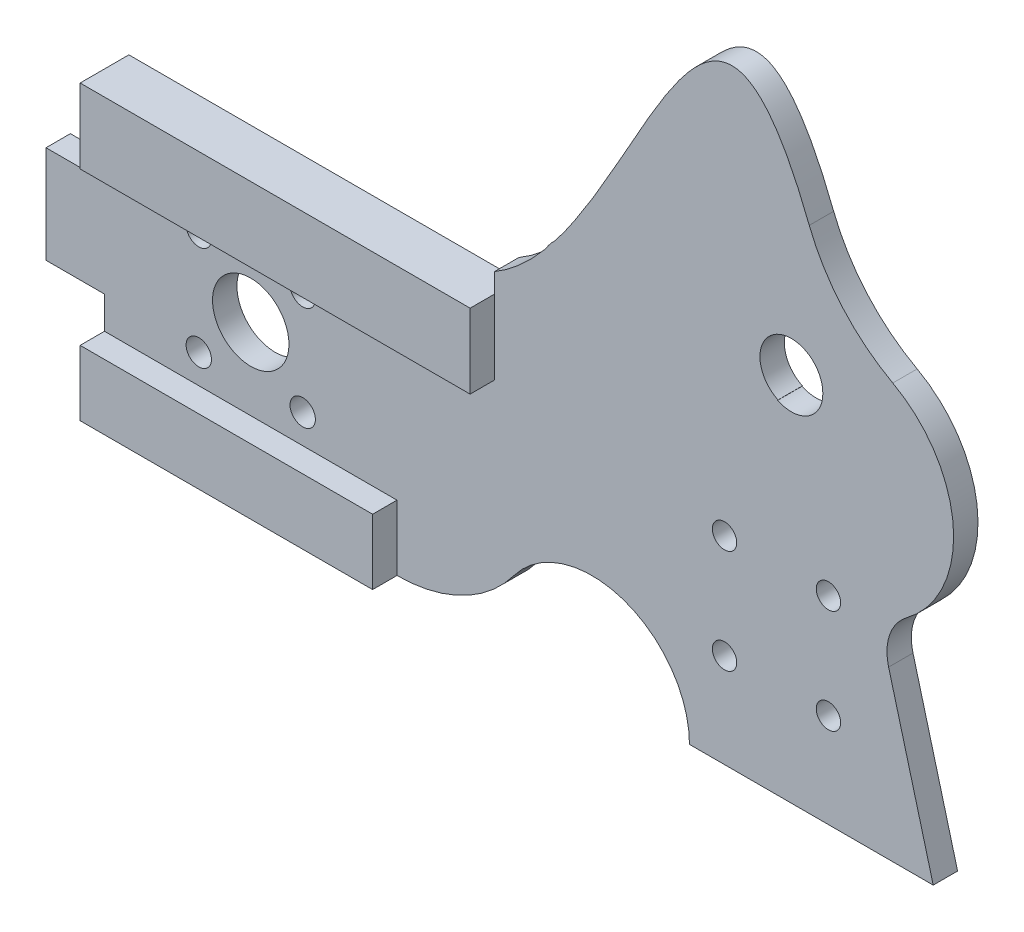
SolidWorks part; units mm, degrees
ref_plane "Front Plane" through (0, 0, 0) normal (0, 0, 1) x (1, 0, 0)
ref_plane "Top Plane" through (0, 0, 0) normal (0, 1, 0) x (1, 0, 0)
ref_plane "Right Plane" through (0, 0, 0) normal (1, 0, 0) x (0, 0, -1)
sketch "Sketch1" plane through (0, 0, 0) normal (0, 0, 1) x (1, 0, 0)
  line L0 (0, 0) -> (107.95, 0)
  line L3 (0, 38.1) -> (0, 25.4)
  line L4 (95.3675, 55.88) -> (0, 38.1)
  line L5 (0, 19.05) -> (100.2273, 19.05) construction
  line L6 (19.05, 19.05) -> (19.05, 28.62) construction
  line L7 (19.05, 19.05) -> (25.817, 25.817) construction
  line L8 (107.95, 0) -> (100.9363, 26.1756)
  line L10 (0, 12.7) -> (0, 0)
  line L11 (0, 25.4) -> (-7.62, 25.4)
  line L13 (0, 12.7) -> (-7.62, 12.7)
  line L14 (-7.62, 25.4) -> (-7.62, 12.7)
  line L15 (100.9363, 26.1756) -> (100.8688, 26.4276)
  arc A0 (100.8688, 26.4276) -> (95.3675, 55.88) centre (95.3675, 40.64) ccw
  circle A1 centre (95.3675, 40.64) radius 4.0957 construction
  circle A2 centre (19.05, 19.05) radius 9.57 construction
  circle A3 centre (25.817, 25.817) radius 1.651
  circle A4 centre (25.817, 12.283) radius 1.651
  circle A5 centre (12.283, 12.283) radius 1.651
  circle A6 centre (12.283, 25.817) radius 1.651
  circle A7 centre (89.4701, 48.2476) radius 4.0958
  point P26 (19.05, 19.05)
  dimension "D1" = 8.1915
  dimension "D5" = 15.24
  dimension "D4" = 19.14
  dimension "D7" = 3.302
  dimension "D11" = 97.0107
  dimension "D2" = 38.1
  dimension "D6" = 107.95
  dimension "D8" = 45
  dimension "D9" = 4
  dimension "D10" = 19.05
  dimension "D12" = 75
  dimension "D14" = 12.7
  dimension "D15" = 12.7
  dimension "D16" = 7.62
extrude "Boss-Extrude1" add sketch "Sketch1" along normal blind 3.175
sketch "Sketch2" plane through (0, 0, 3.175) normal (0, 0, 1) x (1, 0, 0)
  circle A0 centre (95.3675, 40.64) radius 38.1 construction
sketch "Sketch6" plane through (0, 0, 3.175) normal (0, 0, 1) x (1, 0, 0)
  line L0 (0, 0) -> (107.95, 0) construction
  line L1 (50.8, 0) -> (76.2, 0)
  arc A0 (76.2, 0) -> (50.8, 0) centre (63.5, 0) ccw
  dimension "D1" = 25.4
  dimension "D2" = 31.75
extrude "Cut-Extrude2" cut sketch "Sketch6" against normal blind 6.35
sketch "Sketch7" plane through (0, 0, 3.175) normal (0, 0, 1) x (1, 0, 0)
  line L0 (12.283, 25.817) -> (25.817, 12.283) construction
  line L1 (12.283, 12.283) -> (25.817, 25.817) construction
  line L2 (12.283, 25.817) -> (78.4839, 25.817) construction
  line L3 (11.7326, 12.283) -> (12.283, 12.283) construction
  circle A0 centre (19.05, 19.05) radius 4.9784
  circle A4 centre (80.7666, 12.283) radius 1.5875
  circle A5 centre (94.2997, 12.283) radius 1.5875
  circle A6 centre (80.7666, 25.817) radius 1.5875
  circle A7 centre (94.2997, 25.817) radius 1.5875
  dimension "D1" = 9.9568
  dimension "D2" = 3.175
  dimension "D3" = 13.5331
extrude "Cut-Extrude3" cut sketch "Sketch7" against normal through all
fillet "Fillet1" radius 6.35 1 edges at (100.8688, 26.4276, 1.5875)
sketch "Sketch8" plane through (0, 0, 3.175) normal (0, 0, 1) x (1, 0, 0)
  line L1 (0, 38.1) -> (50.8, 38.1)
  line L2 (0, 38.1) -> (0, 50.8)
  line L3 (0, 50.8) -> (50.8, 50.8)
  line L4 (50.8, 38.1) -> (50.8, 50.8)
  dimension "D1" = 50.8
  dimension "D2" = 12.7
extrude "Cut-Extrude4" cut sketch "Sketch8" against normal blind 50.8
sketch "Sketch9" plane through (0, 0, 3.175) normal (0, 0, 1) x (1, 0, 0)
  line L3 (50.8, 40.64) -> (57.15, 40.64)
  line L5 (57.15, 40.64) -> (50.8, 40.64)
  line L6 (57.15, 40.64) -> (57.15, 50.8)
  line L7 (57.15, 50.8) -> (50.8, 50.8)
  line L8 (50.8, 40.64) -> (50.8, 50.8)
  line L9 (0, 38.1) -> (50.8, 38.1) construction
  line M8 (50.8, 47.571) -> (50.8, 38.1)
  line M21 (95.3675, 55.88) -> (50.8, 47.571)
  dimension "D1" = 10.16
  dimension "D2" = 2.54
  dimension "D3" = 6.35
extrude "Cut-Extrude5" cut sketch "Sketch9" against normal blind 19.304 contours L3 L6 M21 M8 region at (54.0583, 44.4092, 3.175)
fillet "Fillet6" radius 6.35 1 edges at (57.15, 40.64, 1.5875)
fillet "Fillet7" radius 6.35 1 edges at (57.15, 48.7549, 1.5875)
fillet "Fillet8" radius 19.05 1 edges at (50.8, 0, 1.5875)
sketch "Sketch12" plane through (0, 0, 3.175) normal (0, 0, 1) x (1, 0, 0)
  line L0 (107.95, 0) -> (146.812, 0) construction
  line L1 (8.0257, 45.4128) -> (80.6683, 75.7903) construction
  line L2 (95.3675, 40.64) -> (80.6683, 75.7903) construction
  line L3 (80.6683, 75.7903) -> (79.4434, 78.7195) construction
  line L4 (50.8, 40.64) -> (85.0271, 40.64)
  line L5 (85.0271, 40.64) -> (95.3675, 55.88)
  arc A0 (61.8128, 49.6242) -> (56.8883, 45.1859) centre (62.9766, 43.3817) ccw construction
  circle A1 centre (19.05, 19.05) radius 28.575 construction
  circle A2 centre (95.3675, 40.64) radius 38.1 construction
  circle A3 centre (80.6683, 75.7903) radius 3.175 construction
  spline S0 degree 3 poles (50.8, 40.64) (70.7778, 52.1788) (78.5943, 111.5434) (95.3675, 55.88) knots 0 0 0 0 1 1 1 1
  dimension "D2" = 6.35
  dimension "D1" = 38.862
extrude "Boss-Extrude2" add sketch "Sketch12" against normal blind 3.175
fillet "Fillet9" radius 24.13 1 edges at (95.3675, 55.88, 1.5875)
sketch "Sketch13" plane through (0, 0, 0) normal (0, 0, -1) x (-1, 0, 0)
  line L0 (0, 38.1) -> (0, 25.4) construction
  line L1 (-50.8, 38.1) -> (0, 38.1)
  line L2 (-50.8, 38.1) -> (-50.8, 28.4023)
  line L3 (-50.8, 28.4023) -> (0, 28.4023)
  line L4 (0, 38.1) -> (0, 28.4023)
  line L5 (0, 12.7) -> (0, 0) construction
  line L6 (0, 8.5046) -> (-38.1, 8.5046)
  line L7 (0, 8.5046) -> (0, 0)
  line L8 (0, 0) -> (-38.1, 0)
  line L9 (-38.1, 8.5046) -> (-38.1, 0)
extrude "Boss-Extrude3" add sketch "Sketch13" against normal blind 6.35
sketch "Sketch14" plane through (0, 0, 3.175) normal (0, 0, 1) x (1, 0, 0)
  circle A0 centre (89.4713, 48.3334) radius 4.0958
  circle A1 centre (94.2997, 25.817) radius 1.5875 construction
  dimension "D1" = 22.5164
  dimension "D2" = 4.8284
extrude "Cut-Extrude6" cut sketch "Sketch14" against normal through all
